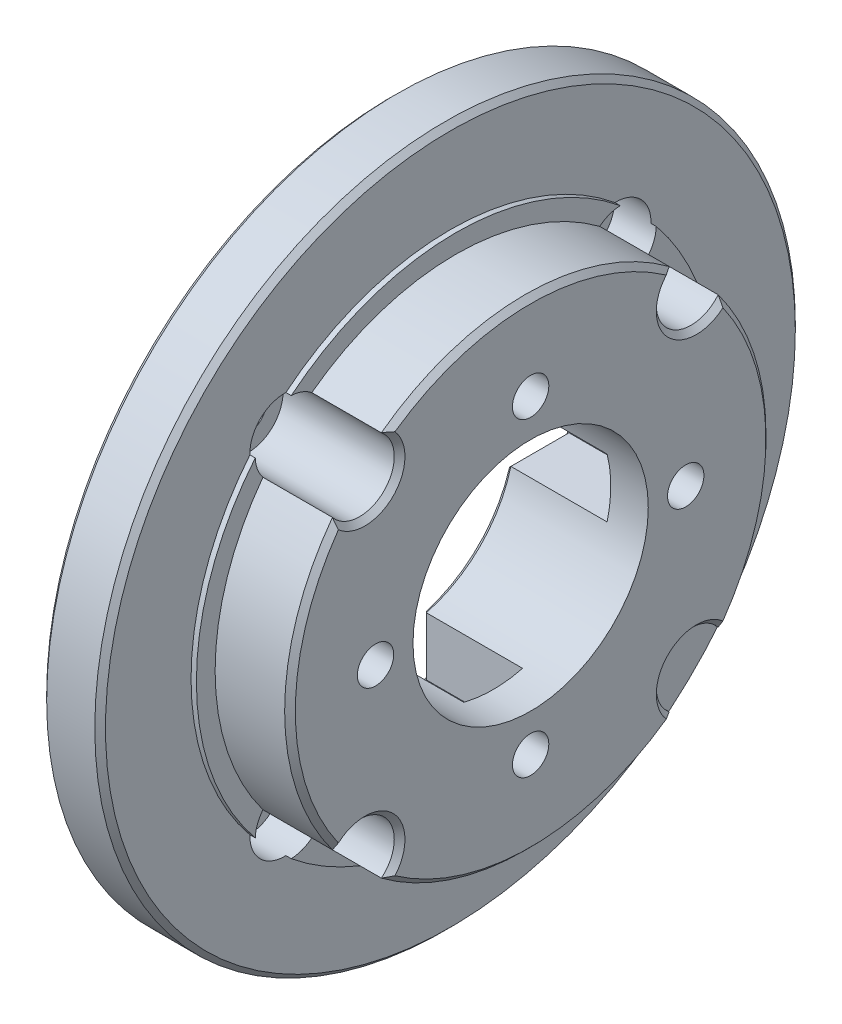
SolidWorks part; units mm, degrees
ref_plane "Ebene vorne" through (0, 0, 0) normal (0, 0, 1) x (1, 0, 0)
ref_plane "Ebene oben" through (0, 0, 0) normal (0, 1, 0) x (1, 0, 0)
ref_plane "Ebene rechts" through (0, 0, 0) normal (1, 0, 0) x (0, 0, -1)
sketch "Sketch1" plane through (0, 0, 0) normal (0, 0, 1) x (1, 0, 0)
  line L0 (0, 0) -> (49.3212, 0) construction
  line L1 (0, 0) -> (0, 32.75)
  line L2 (0, 32.75) -> (5.5, 32.75)
  line L3 (5.5, 32.75) -> (5.5, 24.25)
  line L4 (5.5, 24.25) -> (6, 24.25)
  line L5 (6, 24.25) -> (6, 22.5)
  line L6 (6, 22.5) -> (13, 22.5)
  line L7 (13, 22.5) -> (13, 0)
  line L8 (13, 11) -> (0, 11)
  dimension "D1" = 65.5
  dimension "D2" = 48.5
  dimension "D3" = 45
  dimension "D4" = 0.5
  dimension "D5" = 5.5
  dimension "D6" = 7
  dimension "D7" = 22
revolve "Revolve1" add sketch "Sketch1" angle 360 about L0 region at (5.4743, 19.7433, 0)
hole_wizard "M3 Clearance Hole1" positions "Sketch3" profile "Sketch5" hole size "M3" standard "DIN" end condition through all
sketch "Sketch3" plane through (13, 0, 0) normal (1, 0, 0) x (0, 0, -1)
  circle A0 centre (0, 0) radius 14.5
  point P4 (0, 14.5)
  point P6 (14.5, 0)
  point P8 (0, -14.5)
  point P10 (-14.5, 0)
  dimension "D1" = 29
sketch "Sketch5" plane through (13, 0, 14.5) normal (0, 1, 0) x (0, 0, -1)
  line L0 (0, 0) -> (0, 13)
  line L1 (0, 13) -> (1.7, 13)
  line L2 (1.7, 13) -> (1.7, 0)
  line L5 (1.7, 0) -> (0, 0)
  line L11 (0, -6.35) -> (0, 107.95) construction
  dimension "Thru Hole Dia." = 3.4
  dimension "Thru Hole Depth" = 13
sketch "Sketch6" plane through (0, 0, 0) normal (-1, 0, 0) x (0, 0, 1)
  line L0 (-2.75, 12.9123) -> (-2.75, 10.6507)
  line L1 (0, 11.3246) -> (2.75, 12.9123)
  line L2 (2.75, 12.9123) -> (2.75, 16.0877)
  line L3 (2.75, 16.0877) -> (0, 17.6754)
  line L4 (0, 17.6754) -> (-2.75, 16.0877)
  line L5 (-2.75, 16.0877) -> (-2.75, 12.9123)
  line L6 (-2.75, 12.9123) -> (0, 11.3246)
  line L7 (2.75, 12.9123) -> (2.75, 10.6507)
  line L8 (12.9123, 2.75) -> (10.6507, 2.75)
  line L9 (11.3246, 0) -> (12.9123, -2.75)
  line L10 (12.9123, -2.75) -> (16.0877, -2.75)
  line L11 (16.0877, -2.75) -> (17.6754, 0)
  line L12 (17.6754, 0) -> (16.0877, 2.75)
  line L13 (16.0877, 2.75) -> (12.9123, 2.75)
  line L14 (12.9123, 2.75) -> (11.3246, 0)
  line L15 (12.9123, -2.75) -> (10.6507, -2.75)
  line L16 (2.75, -12.9123) -> (2.75, -10.6507)
  line L17 (0, -11.3246) -> (-2.75, -12.9123)
  line L18 (-2.75, -12.9123) -> (-2.75, -16.0877)
  line L19 (-2.75, -16.0877) -> (0, -17.6754)
  line L20 (0, -17.6754) -> (2.75, -16.0877)
  line L21 (2.75, -16.0877) -> (2.75, -12.9123)
  line L22 (2.75, -12.9123) -> (0, -11.3246)
  line L23 (-2.75, -12.9123) -> (-2.75, -10.6507)
  line L24 (-12.9123, -2.75) -> (-10.6507, -2.75)
  line L25 (-11.3246, 0) -> (-12.9123, 2.75)
  line L26 (-12.9123, 2.75) -> (-16.0877, 2.75)
  line L27 (-16.0877, 2.75) -> (-17.6754, 0)
  line L28 (-17.6754, 0) -> (-16.0877, -2.75)
  line L29 (-16.0877, -2.75) -> (-12.9123, -2.75)
  line L30 (-12.9123, -2.75) -> (-11.3246, 0)
  line L31 (-12.9123, 2.75) -> (-10.6507, 2.75)
  circle A0 centre (0, 14.5) radius 2.75 construction
  circle A1 centre (0, 0) radius 11 construction
  circle A2 centre (0, 0) radius 11
  circle A3 centre (14.5, 0) radius 2.75 construction
  circle A4 centre (0, -14.5) radius 2.75 construction
  circle A5 centre (-14.5, 0) radius 2.75 construction
  circle M8 centre (0, 14.5) radius 1.7
  circle M9 centre (-14.5, 0) radius 1.7
  circle M10 centre (0, -14.5) radius 1.7
  circle M11 centre (14.5, 0) radius 1.7
  circle M13 centre (0, 0) radius 11
  dimension "D1" = 4
extrude "Cut-Extrude1" cut sketch "Sketch6" against normal offset from surface (9.5 mm away) 3.5 contours L5 L6 L1 L2 L3 L4 M8 | L7 L1 L6 L0 M13 | L15 L9 L14 L8 M13 | L13 L14 L9 L10 L11 L12 M11 | L21 L22 L17 L18 L19 L20 M10 | L23 L17 L22 L16 M13 | L31 L25 L30 L24 M13 | L29 L30 L25 L26 L27 L28 M9 region at (0, 12.0669, -1.4047) region at (0, 14.5, -2.666) region at (0, 0, -11.0595) region at (0, 2.6905, 11.7815) region at (0, 1.333, -12.1912) region at (0, 2.666, 14.5) region at (0, -11.0595, 0) region at (0, -12.1912, -1.333) up to face at (13, 14.5, -1.7)
sketch "Sketch7" plane through (13, 0, 0) normal (1, 0, 0) x (0, 0, -1)
  line L1 (-15.5, -15.5) -> (15.5, -15.5)
  line L2 (-15.5, -15.5) -> (-15.5, 15.5)
  line L3 (-15.5, 15.5) -> (15.5, 15.5)
  line L4 (15.5, -15.5) -> (15.5, 15.5)
  line L5 (-15.5, -15.5) -> (15.5, 15.5) construction
  line L6 (-15.5, 15.5) -> (15.5, -15.5) construction
  circle A0 centre (0, 0) radius 21.9203
  circle A1 centre (-15.5, 15.5) radius 3.25
  circle A2 centre (-15.5, -15.5) radius 3.25
  circle A3 centre (15.5, -15.5) radius 3.25
  circle A4 centre (15.5, 15.5) radius 3.25
  dimension "D1" = 31
  dimension "D3" = 6.5
  dimension "D2" = 31
  dimension "D4" = 4
extrude "Cut-Extrude2" cut sketch "Sketch7" against normal up to surface (7.5 mm away) contours A1 | A4 | A3 | A2 up to face at (5.5, 0, 24.25)
hole_wizard "CBORE for M3 Hex Socket Head Cap Screw1" positions "Sketch8" profile "Sketch9" counterbore size "M3" standard "DIN" end condition through all
sketch "Sketch8" plane through (5.5, 0, 0) normal (1, 0, 0) x (0, 0, -1)
  point P0 (-15.5, 15.5)
  point P3 (15.5, 15.5)
  point P6 (15.5, -15.5)
  point P9 (-15.5, -15.5)
sketch "Sketch9" plane through (5.5, 15.5, 15.5) normal (0, 1, 0) x (0, 0, -1)
  line L0 (0, 0) -> (0, 5.5)
  line L1 (0, 5.5) -> (1.7, 5.5)
  line L3 (1.7, 5.5) -> (1.7, 3.4)
  line L4 (1.7, 3.4) -> (3.25, 3.4)
  line L5 (3.25, 3.4) -> (3.25, 0)
  line L7 (3.25, 0) -> (0, 0)
  line L11 (0, -6.35) -> (0, 107.95) construction
  dimension "Thru Hole Dia." = 3.4
  dimension "Thru Hole Depth" = 5.5
  dimension "C'Bore Dia." = 6.5
  dimension "C'Bore Depth" = 3.4
chamfer "Chamfer1" distance 0.5 angle 45 30 edges at (0, 16.8816, 1.375) (0, 16.8816, -1.375) (0, 13.3692, -2.75) (0, 7.7782, -7.7782) (0, 2.75, -13.3692) (0, 1.375, -16.8816) (0, -1.375, -16.8816) (0, -2.75, -13.3692) (0, -7.7782, -7.7782) (0, -13.3692, -2.75) (0, -16.8816, -1.375) (0, -16.8816, 1.375) (0, 13.3692, 2.75) (0, 7.7782, 7.7782) (0, 2.75, 13.3692) (0, 1.375, 16.8816) (0, -1.375, 16.8816) (0, -2.75, 13.3692) (0, -7.7782, 7.7782) (0, -13.3692, 2.75) (0, 0, 32.75) (5.5, 0, 32.75) (13, 0, 22.5) (13, 13.2019, 13.2019) (13, 22.5, 0) (13, 13.2019, -13.2019) (13, 0, -22.5) (13, -13.2019, -13.2019) (13, -22.5, 0) (13, -13.2019, 13.2019)
